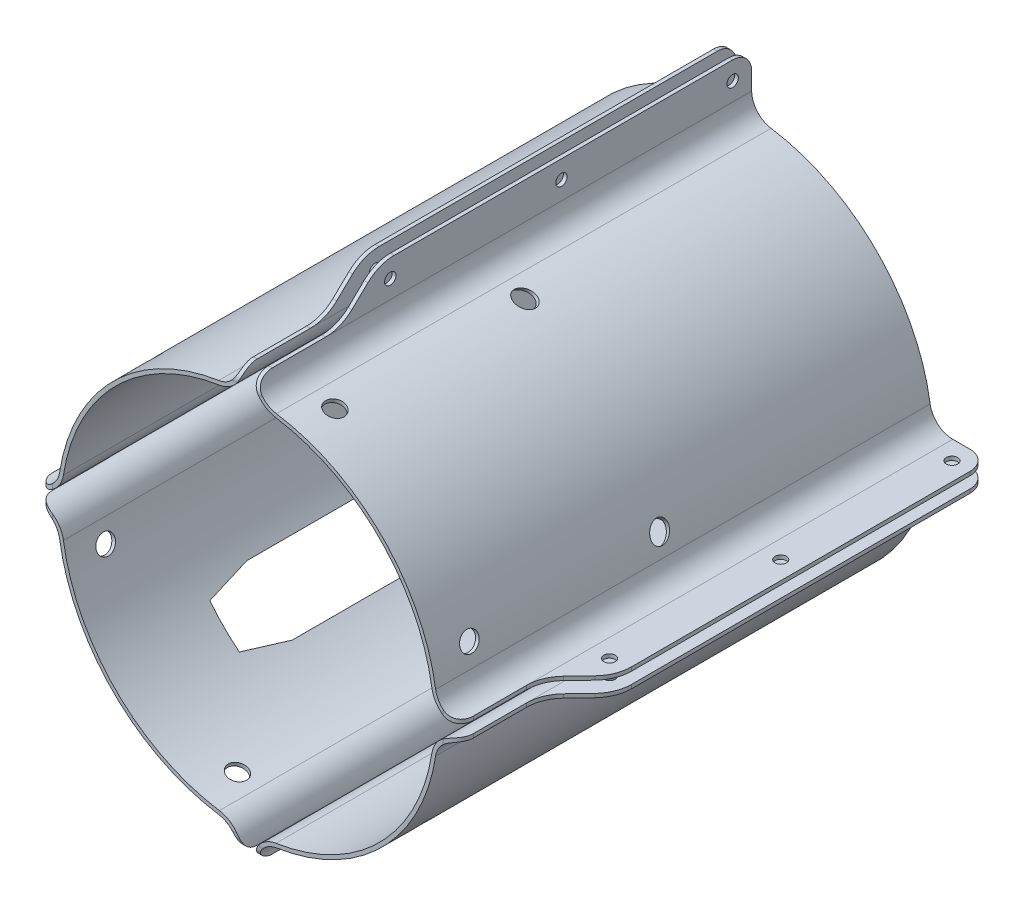
SolidWorks part; units mm, degrees
ref_plane "Спереди" through (0, 0, 0) normal (0, 0, 1) x (1, 0, 0)
ref_plane "Сверху" through (0, 0, 0) normal (0, 1, 0) x (1, 0, 0)
ref_plane "Справа" through (0, 0, 0) normal (1, 0, 0) x (0, 0, -1)
sketch "Эскиз1" plane through (0, 0, 0) normal (0, 0, 1) x (1, 0, 0)
  line L0 (0, 0) -> (0, 63.1749) construction
  line L1 (2.5, 55.3512) -> (2.5, 64.9375)
  line L2 (1.5, 64.9375) -> (1.5, 55.3512)
  line L3 (1.5, 64.9375) -> (2.5, 64.9375)
  line L4 (-1.5, 64.9375) -> (-2.5, 64.9375)
  line L5 (-1.5, 64.9375) -> (-1.5, 55.3512)
  line L6 (-2.5, 55.3512) -> (-2.5, 64.9375)
  line L7 (55.3512, -2.5) -> (64.9375, -2.5)
  line L8 (64.9375, -1.5) -> (55.3512, -1.5)
  line L9 (64.9375, -1.5) -> (64.9375, -2.5)
  line L10 (64.9375, 1.5) -> (64.9375, 2.5)
  line L11 (64.9375, 1.5) -> (55.3512, 1.5)
  line L12 (55.3512, 2.5) -> (64.9375, 2.5)
  line L13 (-2.5, -55.3512) -> (-2.5, -64.9375)
  line L14 (-1.5, -64.9375) -> (-1.5, -55.3512)
  line L15 (-1.5, -64.9375) -> (-2.5, -64.9375)
  line L16 (1.5, -64.9375) -> (2.5, -64.9375)
  line L17 (1.5, -64.9375) -> (1.5, -55.3512)
  line L18 (2.5, -55.3512) -> (2.5, -64.9375)
  line L19 (-55.3512, 2.5) -> (-64.9375, 2.5)
  line L20 (-64.9375, 1.5) -> (-55.3512, 1.5)
  line L21 (-64.9375, 1.5) -> (-64.9375, 2.5)
  line L22 (-64.9375, -1.5) -> (-64.9375, -2.5)
  line L23 (-64.9375, -1.5) -> (-55.3512, -1.5)
  line L24 (-55.3512, -2.5) -> (-64.9375, -2.5)
  arc A0 (-7.5893, 49.4207) -> (-49.4207, 7.5893) centre (0, 0) ccw
  arc A1 (-7.4375, 48.4323) -> (-48.4323, 7.4375) centre (0, 0) ccw
  arc A2 (-7.5893, 49.4207) -> (-2.5, 55.3512) centre (-8.5, 55.3512) ccw
  arc A3 (-7.4375, 48.4323) -> (-1.5, 55.3512) centre (-8.5, 55.3512) ccw
  arc A4 (7.4375, 48.4323) -> (1.5, 55.3512) centre (8.5, 55.3512) cw
  arc A5 (7.5893, 49.4207) -> (2.5, 55.3512) centre (8.5, 55.3512) cw
  arc A6 (49.4207, 7.5893) -> (55.3512, 2.5) centre (55.3512, 8.5) ccw
  arc A7 (48.4323, 7.4375) -> (55.3512, 1.5) centre (55.3512, 8.5) ccw
  arc A8 (48.4323, -7.4375) -> (55.3512, -1.5) centre (55.3512, -8.5) cw
  arc A9 (49.4207, -7.5893) -> (55.3512, -2.5) centre (55.3512, -8.5) cw
  arc A10 (7.5893, -49.4207) -> (2.5, -55.3512) centre (8.5, -55.3512) ccw
  arc A11 (7.4375, -48.4323) -> (1.5, -55.3512) centre (8.5, -55.3512) ccw
  arc A12 (-7.4375, -48.4323) -> (-1.5, -55.3512) centre (-8.5, -55.3512) cw
  arc A13 (-7.5893, -49.4207) -> (-2.5, -55.3512) centre (-8.5, -55.3512) cw
  arc A14 (-49.4207, -7.5893) -> (-55.3512, -2.5) centre (-55.3512, -8.5) ccw
  arc A15 (-48.4323, -7.4375) -> (-55.3512, -1.5) centre (-55.3512, -8.5) ccw
  arc A16 (-48.4323, 7.4375) -> (-55.3512, 1.5) centre (-55.3512, 8.5) cw
  arc A17 (-49.4207, 7.5893) -> (-55.3512, 2.5) centre (-55.3512, 8.5) cw
  arc A18 (-49.4207, -7.5893) -> (-7.5893, -49.4207) centre (0, 0) ccw
  arc A19 (-48.4323, -7.4375) -> (-7.4375, -48.4323) centre (0, 0) ccw
  arc A20 (7.4375, -48.4323) -> (48.4323, -7.4375) centre (0, 0) ccw
  arc A21 (7.5893, -49.4207) -> (49.4207, -7.5893) centre (0, 0) ccw
  arc A22 (49.4207, 7.5893) -> (7.5893, 49.4207) centre (0, 0) ccw
  arc A23 (48.4323, 7.4375) -> (7.4375, 48.4323) centre (0, 0) ccw
  point P13 (-2.5, 49.9375)
  point P16 (-1.5, 48.977)
  point P19 (1.5, 48.977)
  point P22 (2.5, 49.9375)
  point P74 (0, 0)
  dimension "D1" = 100
  dimension "D6" = 6
  dimension "D7" = 7
  dimension "D8" = 7
  dimension "D9" = 6
  dimension "D2" = 1
  dimension "D3" = 15
  dimension "D4" = 5
  dimension "D5" = 1
  dimension "D10" = 4
extrude "Бобышка-Вытянуть1" add sketch "Эскиз1" along normal blind 130
sketch "Эскиз2" plane through (2.5, 0, 0) normal (1, 0, 0) x (0, 0, -1)
  line L1 (0, 55.3512) -> (0, 64.9375) construction
  line L2 (-130, 64.9375) -> (-98, 64.9375)
  line L3 (-130, 64.9375) -> (0, 64.9375) construction
  line L4 (-98, 64.9375) -> (-108, 55.3512)
  line L5 (-130, 55.3512) -> (0, 55.3512) construction
  line L6 (-108, 55.3512) -> (-130, 55.3512)
  line L7 (-130, 64.9375) -> (-130, 55.3512)
  circle A0 centre (-5, 60.1443) radius 1.5
  circle A1 centre (-50, 60.1443) radius 1.5
  circle A2 centre (-95, 60.1443) radius 1.5
  point P12 (0, 60.1443)
  dimension "D3" = 3
  dimension "D1" = 45
  dimension "D2" = 45
  dimension "D4" = 5
  dimension "D5" = 13
  dimension "D6" = 3
extrude "Вырез-Вытянуть1" cut sketch "Эскиз2" against normal blind 130
fillet "Скругление1" radius 4 1 edges at (2, 55.3512, 130)
fillet "Скругление2" radius 4 1 edges at (-2, 55.3512, 130)
fillet "Скругление5" radius 10 1 edges at (-2, 64.9375, 98)
fillet "Скругление6" radius 10 1 edges at (2, 64.9375, 98)
fillet "Скругление7" radius 5 1 edges at (-2, 64.9375, 0)
fillet "Скругление8" radius 5 1 edges at (2, 64.9375, 0)
sketch "Эскиз3" plane through (0, 2.5, 0) normal (0, 1, 0) x (1, 0, 0)
  line L0 (-64.9375, -130) -> (-64.9375, -98)
  line L1 (-64.9375, -98) -> (-55.3512, -108)
  line L2 (-55.3512, -108) -> (-55.3512, -130)
  line L3 (-64.9375, -130) -> (-55.3512, -130)
  circle A0 centre (-60.1443, -5) radius 1.5
  circle A1 centre (-60.1443, -50) radius 1.5
  circle A2 centre (-60.1443, -95) radius 1.5
  point P9 (-60.1443, 0)
extrude "Вырез-Вытянуть2" cut sketch "Эскиз3" against normal up to surface (5 mm away)
pattern_circular "Круговой массив6" count 4 over 360 about axis through (0, 0, 130) along (0, 0, -1) of "Вырез-Вытянуть2"
fillet "Скругление9" radius 4 1 edges at (-55.3512, 2, 130)
fillet "Скругление10" radius 10 2 edges at (-64.9375, 2, 98) (-55.3512, 2, 108)
fillet "Скругление11" radius 5 1 edges at (-64.9375, 2, 0)
fillet "Скругление12" radius 5 2 edges at (-64.9375, -2, 0) (-2, -64.9375, 0)
fillet "Скругление13" radius 4 2 edges at (-2, -55.3512, 130) (-55.3512, -2, 130)
fillet "Скругление14" radius 10 4 edges at (-55.3512, -2, 108) (-64.9375, -2, 98) (-2, -64.9375, 98) (-2, -55.3512, 108)
fillet "Скругление15" radius 5 2 edges at (64.9375, -2, 0) (2, -64.9375, 0)
fillet "Скругление16" radius 5 1 edges at (64.9375, 2, 0)
fillet "Скругление17" radius 10 3 edges at (2, 55.3512, 108) (55.3512, 2, 108) (64.9375, 2, 98)
fillet "Скругление18" radius 10 1 edges at (-2, 55.3512, 108)
fillet "Скругление19" radius 4 1 edges at (55.3512, 2, 130)
fillet "Скругление20" radius 10 4 edges at (55.3512, -2, 108) (64.9375, -2, 98) (2, -55.3512, 108) (2, -64.9375, 98)
fillet "Скругление21" radius 4 2 edges at (2, -55.3512, 130) (55.3512, -2, 130)
ref_plane "Плоскость1" through (0, 0, 0) normal (-0.7071, 0.7071, 0) x (0.7071, 0.7071, 0)
sketch "Эскиз4" plane through (0, 0, 0) normal (-0.7071, 0.7071, 0) x (0.7071, 0.7071, 0)
  line L0 (-29.5793, -130) -> (29.5793, -130) construction
  circle A0 centre (0, -120) radius 2.5
  dimension "D1" = 5
  dimension "D2" = 10
extrude "Вырез-Вытянуть3" cut sketch "Эскиз4" against normal through all
pattern_circular "Круговой массив7" count 6 over 360 about axis through (0, 0, 130) along (0, 0, -1) of "Вырез-Вытянуть3"
ref_plane "Плоскость2" through (-0.3597, -0.0964, 0) normal (-0.7071, -0.7071, 0) x (0.7071, -0.7071, 0)
sketch "Эскиз6" plane through (-0.3597, -0.0964, 0) normal (-0.7071, -0.7071, 0) x (0.7071, -0.7071, 0)
  line L0 (5.5, 101.5) -> (-5.5, 101.5) construction
  line L1 (5.5, 101.5) -> (-5.5, 101.5)
  line L2 (-5.5, 15) -> (5.5, 15) construction
  line L3 (-5.5, 15) -> (5.5, 15)
  line L4 (-8.5, 26.5) -> (8.5, 26.5) construction
  line L5 (-8.5, 26.5) -> (8.5, 26.5)
  line L6 (8.5, 90) -> (-8.5, 90) construction
  line L7 (8.5, 90) -> (-8.5, 90)
  line L8 (5.5, 101.5) -> (8.5, 90)
  line L10 (8.5, 26.5) -> (5.5, 15)
  line L11 (-5.5, 15) -> (-8.5, 26.5)
  line L12 (-5.5, 101.5) -> (-8.5, 90)
  line L13 (-8.5, 90) -> (8.5, 90)
  line L14 (-8.5, 90) -> (-8.5, 26.5)
  line L15 (-8.5, 26.5) -> (8.5, 26.5)
  line L16 (8.5, 90) -> (8.5, 26.5)
extrude "Вырез-Вытянуть4" cut sketch "Эскиз6" along normal through all contours L16 L7 L14 L5 | L11 L3 L10 L5 | L1 L12 L7 L8
sketch "Эскиз7" plane through (-0.3597, -0.0964, 0) normal (-0.7071, -0.7071, 0) x (0.7071, -0.7071, 0)
  line L0 (29.7654, 130) -> (29.7654, 0) construction
  line L1 (-29.3931, 130) -> (-29.3931, 0) construction
  line L2 (-29.3931, 130) -> (-29.3931, 0)
  line L3 (29.7654, 130) -> (29.7654, 0)
  line L6 (-29.3931, 0) -> (29.7654, 0)
  line L7 (0.1862, 0) -> (0.1862, 130) construction
  line L8 (29.7654, 130) -> (-29.3931, 130) construction
  circle A0 centre (25.1862, 70) radius 2.5
  circle A1 centre (-24.8138, 70) radius 2.5
  point P8 (1.0334, 0)
  dimension "D1" = 5
  dimension "D2" = 5
  dimension "D3" = 50
  dimension "D5" = 25
  dimension "D6" = 70
  dimension "D4" = 59.1585
extrude "Вырез-Вытянуть5" cut sketch "Эскиз7" against normal blind 72 contours A1 | A0
equation "\"D5@Эскиз1\"=\"D2@Эскиз1\""
